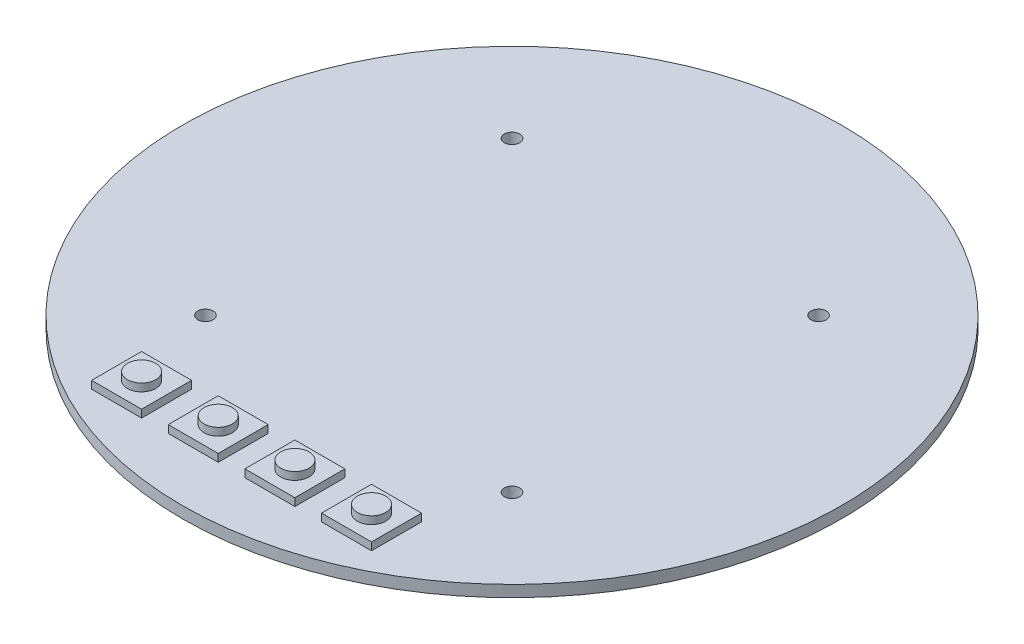
SolidWorks part; units mm, degrees
ref_plane "Front Plane" through (0, 0, 0) normal (0, 0, 1) x (1, 0, 0)
ref_plane "Top Plane" through (0, 0, 0) normal (0, 1, 0) x (1, 0, 0)
ref_plane "Right Plane" through (0, 0, 0) normal (1, 0, 0) x (0, 0, -1)
sketch "草图1" plane through (0, 0, 0) normal (0, 1, 0) x (1, 0, 0)
  line L0 (0, 61.0249) -> (0, -66.3314) construction
  line L1 (-66.0193, 0) -> (59.152, 0) construction
  circle A0 centre (0, 0) radius 43
  circle A1 centre (-20, 20) radius 1
  circle A2 centre (-20, -20) radius 1
  circle A3 centre (20, -20) radius 1
  circle A4 centre (20, 20) radius 1
  dimension "D1" = 86
  dimension "D2" = 2
  dimension "D3" = 40
  dimension "D4" = 40
extrude "凸台-拉伸1" add sketch "草图1" along normal mid plane 1.5
sketch "草图3" plane through (0, 0.75, 0) normal (0, 1, 0) x (1, 0, 0)
  line L0 (-61.8512, 0) -> (55.9059, 0) construction
  line L1 (-19.0828, -35.7682) -> (-12.562, -35.7682)
  line L2 (-19.0828, -35.7682) -> (-19.0828, -29.2475)
  line L3 (-19.0828, -29.2475) -> (-12.562, -29.2475)
  line L4 (-12.562, -35.7682) -> (-12.562, -29.2475)
  line L5 (-19.0828, -35.7682) -> (-12.562, -29.2475) construction
  line L6 (-19.0828, -29.2475) -> (-12.562, -35.7682) construction
  circle A0 centre (-15.8224, -32.5079) radius 1.8483
  point P0 (-15.8224, -32.5079)
extrude "凸台-拉伸2" add sketch "草图3" along normal blind 1 contours L1 L4 L3 L2 A0 region at (-18.9906, 0.75, 32.5079)
extrude "凸台-拉伸3" add sketch "草图3<3>" along normal blind 2 contours A0 region at (-15.8224, 0.75, 32.5079)
sketch "草图3<3>" plane through (0, 0.75, 0) normal (0, 1, 0) x (1, 0, 0) same geometry as "草图3"
pattern_linear "阵列(线性)1" count 4 spacing 10 along (1, 0, 0) of "凸台-拉伸2", "凸台-拉伸3"
